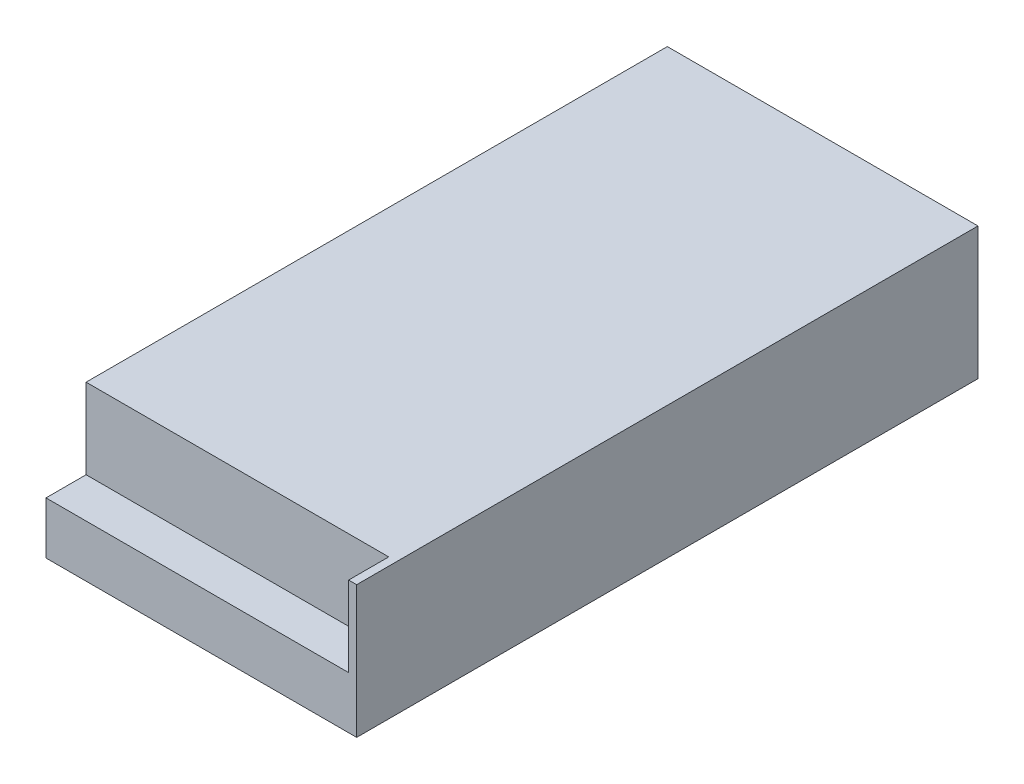
SolidWorks part; units mm, degrees
ref_plane "Front Plane" through (0, 0, 0) normal (0, 0, 1) x (1, 0, 0)
ref_plane "Top Plane" through (0, 0, 0) normal (0, 1, 0) x (1, 0, 0)
ref_plane "Right Plane" through (0, 0, 0) normal (1, 0, 0) x (0, 0, -1)
sketch "Sketch1" plane through (0, 0, 0) normal (0, 1, 0) x (1, 0, 0)
  line L1 (0, 0) -> (98.425, 0)
  line L2 (0, 0) -> (0, 196.85)
  line L3 (0, 196.85) -> (98.425, 196.85)
  line L4 (98.425, 0) -> (98.425, 196.85)
  dimension "D1" = 98.425
  dimension "D2" = 196.85
extrude "Boss-Extrude1" add sketch "Sketch1" along normal blind 41.91
sketch "Sketch2" plane through (98.425, 0, 0) normal (1, 0, 0) x (0, 0, -1)
  line L0 (0, 41.91) -> (0, 0) construction
  line L1 (0, 41.91) -> (12.7, 41.91)
  line L2 (0, 41.91) -> (0, 16.51)
  line L3 (0, 16.51) -> (12.7, 16.51)
  line L4 (12.7, 41.91) -> (12.7, 16.51)
  line L5 (0, 41.91) -> (196.85, 41.91) construction
  dimension "D1" = 12.7
  dimension "D2" = 25.4
extrude "Cut-Extrude1" cut sketch "Sketch2" along normal offset from surface (95.885 mm away) 2.54 from surface up to face at (98.425, 20.955, -98.425) starting at face at (0, 20.955, -98.425)
